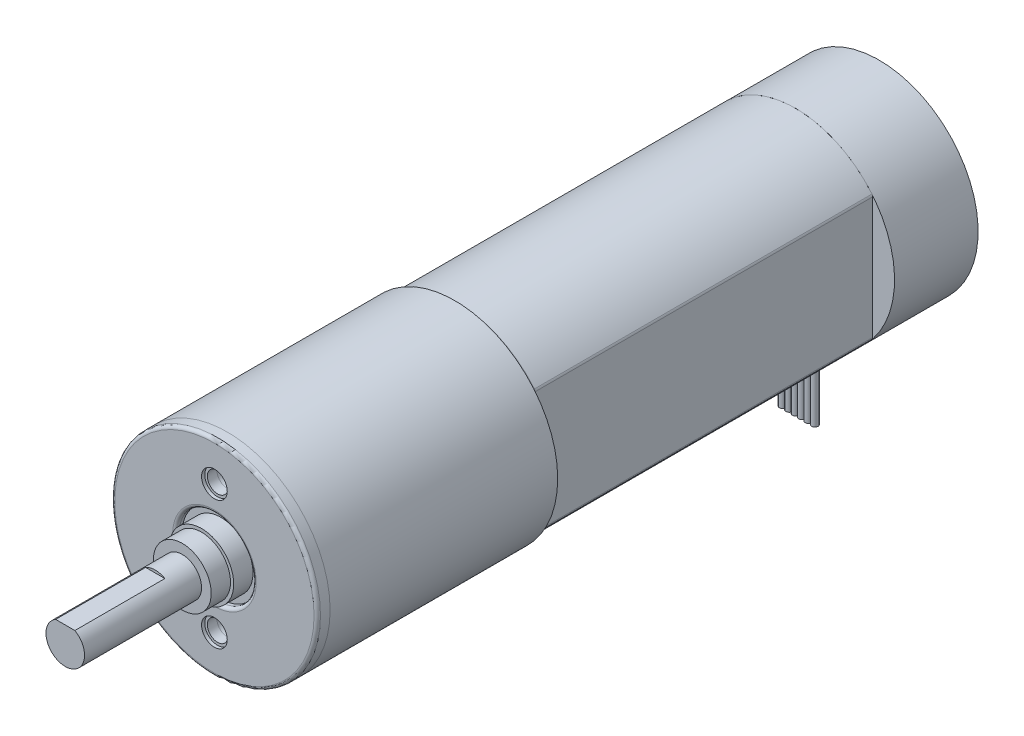
SolidWorks part; units mm, degrees
material "AISI 1035 鋼 (SS)"
ref_plane "前基準面" through (0, 0, 0) normal (0, 0, 1) x (1, 0, 0)
ref_plane "上基準面" through (0, 0, 0) normal (0, 1, 0) x (1, 0, 0)
ref_plane "右基準面" through (0, 0, 0) normal (1, 0, 0) x (0, 0, -1)
sketch "草圖1" plane through (0, 0, 0) normal (0, 0, 1) x (1, 0, 0)
  circle A0 centre (0, 0) radius 7.7
  dimension "D1" = 15.4
extrude "填料-伸長1" add sketch "草圖1" along normal blind 26.5
sketch "草圖2" plane through (0, 0, 26.5) normal (0, 0, 1) x (1, 0, 0)
  line L0 (-6, 4.826) -> (-6, -4.826)
  line L1 (6, 4.826) -> (6, -4.826)
  circle A0 centre (0, 0) radius 7.7 construction
  arc A1 (-6, 4.826) -> (-6, -4.826) centre (0, 0) ccw
  arc A2 (6, 4.826) -> (6, -4.826) centre (0, 0) cw
  circle M3 centre (0, 0) radius 7.7
  dimension "D1" = 12
extrude "除料-伸長1" cut sketch "草圖2" against normal through all contours L0 M3 | L1 M3
fillet "圓角1" radius 0.25 8 edges at (6, -4.826, 13.25) (6, 4.826, 13.25) (-6, 4.826, 13.25) (-6, -4.826, 13.25) (6, 0, 26.5) (0, 7.7, 26.5) (0, -7.7, 26.5) (-6, 0, 26.5)
sketch "草圖4" plane through (0, 0, 26.5) normal (0, 0, 1) x (1, 0, 0)
  circle A0 centre (0, 0) radius 8
  dimension "D1" = 16
extrude "填料-伸長2" add sketch "草圖4" along normal blind 17.7
sketch "草圖5" plane through (0, 0, 44.2) normal (0, 0, 1) x (1, 0, 0)
  circle A1 centre (0, 0) radius 8
  circle A2 centre (0, 0) radius 8
  dimension "D1" = 0
extrude "填料-伸長3" add sketch "草圖5" along normal blind 1 separate body
sketch "草圖6" plane through (0, 0, 45.2) normal (0, 0, 1) x (1, 0, 0)
  circle A0 centre (0, 0) radius 3
  circle A1 centre (0, 0) radius 8 construction
  dimension "D1" = 6
extrude "除料-伸長2" cut sketch "草圖6" against normal blind 0.5
fillet "圓角3" radius 0.25 2 edges at (8, 0, 45.2) (3, 0, 45.2)
sketch "草圖7" plane through (0, 0, 44.7) normal (0, 0, 1) x (1, 0, 0)
  circle A0 centre (0, 0) radius 2.5
  dimension "D1" = 5
extrude "填料-伸長4" add sketch "草圖7" along normal blind 1.5
sketch "草圖8" plane through (0, 0, 46.2) normal (0, 0, 1) x (1, 0, 0)
  circle A0 centre (0, 0) radius 2.25
  dimension "D1" = 4.5
extrude "填料-伸長5" add sketch "草圖8" along normal blind 1.5 separate body
sketch "草圖9" plane through (0, 0, 47.7) normal (0, 0, 1) x (1, 0, 0)
  circle A0 centre (0, 0) radius 1.5
  dimension "D1" = 3
extrude "填料-伸長6" add sketch "草圖9" along normal blind 9.1
sketch "草圖10" plane through (0, 0, 56.8) normal (0, 0, 1) x (1, 0, 0)
  line L0 (-0.7483, 1.3) -> (0.7483, 1.3)
  circle A1 centre (0, 0) radius 1.5 construction
  circle A2 centre (0, 0) radius 1.5 construction
  arc A3 (-0.7483, 1.3) -> (0.7483, 1.3) centre (0, 0) cw
  circle M2 centre (0, 0) radius 1.5
  dimension "D1" = 1.3
extrude "除料-伸長3" cut sketch "草圖10" against normal blind 7 contours L0 M2
hole_wizard "M2x0.4 螺紋孔1" positions "草圖13" profile "草圖15" tap size "M2x0.4" standard "Ansi Metric"
sketch "草圖13" plane through (0, 0, 45.2) normal (0, 0, 1) x (1, 0, 0)
  line L0 (0, -5) -> (0, 5) construction
  point P1 (0, -5)
  point P2 (0, 5)
  dimension "D1" = 10
sketch "草圖15" plane through (0, -5, 45.2) normal (1, 0, 0) x (0, -1, 0)
  line L0 (0, 0) -> (0, 3.4807)
  line L1 (0, 3.4807) -> (0.8, 3)
  line L2 (0.8, 3) -> (0.8, 0)
  line L5 (0.8, 0) -> (0, 0)
  line L10 (0, 3.4807) -> (-0.8, 3) construction
  line L11 (0, -6.35) -> (0, 107.95) construction
  dimension "螺孔鑽直徑" = 1.6
  dimension "螺孔鑽深度" = 3
  dimension "導頭角度" = 118
sketch "草圖16" plane through (0, 0, 45.2) normal (0, 0, 1) x (1, 0, 0)
  circle A0 centre (0, -5) radius 1
  circle A1 centre (0, 5) radius 1
  dimension "D1" = 2
extrude "除料-伸長4" cut sketch "草圖16" against normal blind 0.25
sketch "草圖17" plane through (0, 0, 0) normal (0, 0, -1) x (-1, 0, 0)
  line L0 (-5.75, 4.632) -> (-5.75, -4.632)
  line L1 (5.75, -4.632) -> (5.75, 4.632)
  line L2 (-5.75, 0) -> (5.75, 0) construction
  line L3 (-5.9853, 4.8215) -> (5.9853, -4.8215) construction
  line L4 (5.9853, 4.8215) -> (-5.9853, -4.8215) construction
  arc A0 (-5.75, 4.632) -> (5.75, 4.632) centre (0, 0) cw
  arc A1 (-5.943, 4.8961) -> (-6, 4.7371) centre (-5.75, 4.7371) ccw construction
  arc A2 (5.943, -4.8961) -> (6, -4.7371) centre (5.75, -4.7371) ccw construction
  arc A3 (6, 4.7371) -> (5.943, 4.8961) centre (5.75, 4.7371) ccw construction
  arc A4 (-6, -4.7371) -> (-5.943, -4.8961) centre (-5.75, -4.7371) ccw construction
  arc A5 (-5.75, -4.632) -> (5.75, -4.632) centre (0, 0) ccw
  dimension "D1" = 11.5
extrude "除料-伸長5" cut sketch "草圖17" against normal blind 0.75 contours L0 A5 L1 A0
sketch "草圖18" plane through (0, 0, 0.75) normal (0, 0, -1) x (-1, 0, 0)
  circle A0 centre (0, 0) radius 2.5
  dimension "D1" = 5
extrude "填料-伸長7" add sketch "草圖18" along normal blind 2.5
fillet "圓角4" radius 0.25 1 edges at (-2.5, 0, -1.75)
sketch "草圖19" plane through (0, 0, 0.75) normal (0, 0, -1) x (-1, 0, 0)
  line L0 (0, 0) -> (0, 6) construction
  circle A0 centre (0, 6) radius 0.5
  circle A1 centre (0, 0) radius 2.5 construction
  dimension "D1" = 6
  dimension "D2" = 1
extrude "填料-伸長8" add sketch "草圖19" along normal blind 0.5
sketch "草圖20" plane through (0, 0, 0.25) normal (0, 0, -1) x (-1, 0, 0)
  line L1 (-0.3, 5.9) -> (0.3, 5.9)
  line L2 (-0.3, 5.9) -> (-0.3, 6.1)
  line L3 (-0.3, 6.1) -> (0.3, 6.1)
  line L4 (0.3, 5.9) -> (0.3, 6.1)
  line L5 (-0.3, 5.9) -> (0.3, 6.1) construction
  line L6 (-0.3, 6.1) -> (0.3, 5.9) construction
  point P0 (0, 6)
  dimension "D1" = 0.2
  dimension "D2" = 0.6
extrude "填料-伸長9" add sketch "草圖20" along normal blind 3
sketch "草圖21" plane through (0, 5.9, 0) normal (0, -1, 0) x (1, 0, 0)
  line L0 (0.3, -2.75) -> (-0.3, -2.75) construction
  line L1 (0, 0) -> (0, -2.25) construction
  circle A0 centre (0, -2.25) radius 0.15
  dimension "D1" = 0.3
  dimension "D2" = 0.5
extrude "除料-伸長6" cut sketch "草圖21" against normal through all
fillet "圓角5" radius 0.3 2 edges at (-0.3, 6, -2.75) (0.3, 6, -2.75)
pattern_circular "環狀複製排列1" count 2 over 360 about axis through (0, 0, 0) along (0, 0, 1) of "填料-伸長9", "填料-伸長8", "除料-伸長6", "圓角5"
sketch "草圖23" plane through (0, 0, 0) normal (0, 0, -1) x (-1, 0, 0)
  circle A0 centre (0, 0) radius 7.7
  dimension "D1" = 15.4
extrude "填料-伸長10" add sketch "草圖23" along normal blind 6.5 separate body
sketch "草圖25" plane through (0, -6.1, 0) normal (0, -1, 0) x (1, 0, 0)
  line L0 (-5.943, 0) -> (5.943, 0) construction
  line L1 (1.5, 0) -> (-1.5, 0)
  line L2 (1.5, 0) -> (1.5, -0.5)
  line L3 (1.5, -0.5) -> (-1.5, -0.5)
  line L4 (-1.5, 0) -> (-1.5, -0.5)
  dimension "D1" = 3
  dimension "D2" = 0.5
extrude "除料-伸長7" cut sketch "草圖25" against normal blind 3 and the other way through all from offset 0
sketch "草圖26" plane through (0, -3.1, 0) normal (0, -1, 0) x (1, 0, 0)
  line L0 (-5.943, 0) -> (5.943, 0) construction
  line L1 (-1.5, 0) -> (-1.5, -0.5) construction
  circle A0 centre (-1.25, -0.25) radius 0.25
  point P2 (0, 0)
  dimension "D1" = 0.5
extrude "填料-伸長13" add sketch "草圖26" along normal blind 10 separate body
pattern_linear "直線複製排列1" count 6 spacing 0.5 along (1, 0, 0) of "填料-伸長13"
